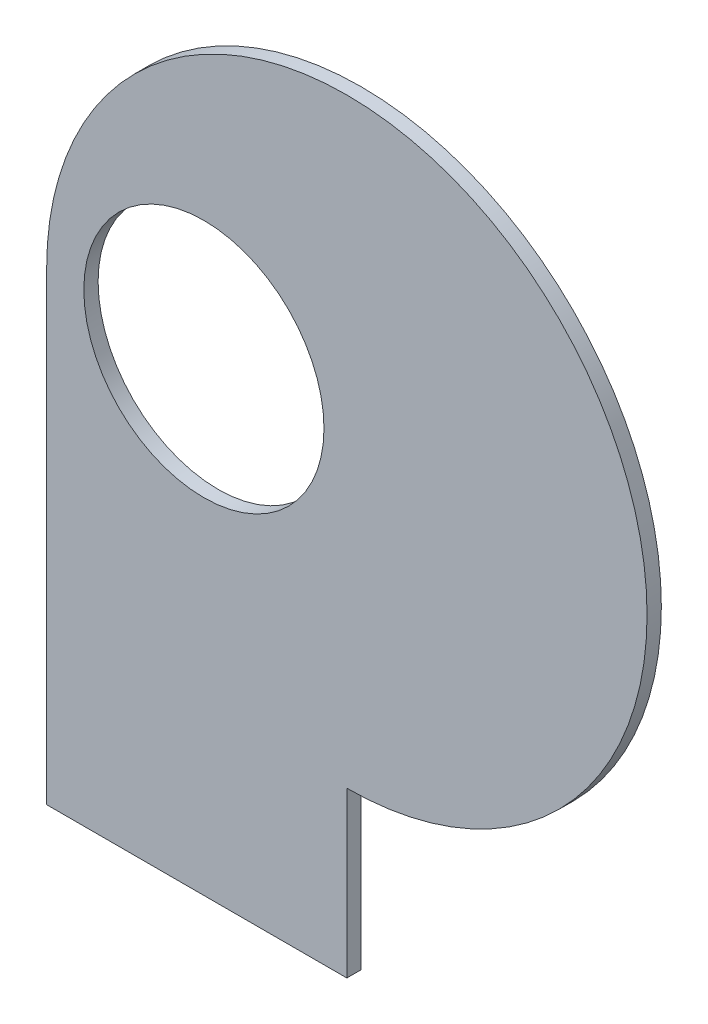
SolidWorks part; units mm, degrees
ref_plane "Front Plane" through (0, 0, 0) normal (0, 0, 1) x (1, 0, 0)
ref_plane "Top Plane" through (0, 0, 0) normal (0, 1, 0) x (1, 0, 0)
ref_plane "Right Plane" through (0, 0, 0) normal (1, 0, 0) x (0, 0, -1)
sketch "Sketch1" plane through (0, 0, 0) normal (0, 0, 1) x (1, 0, 0)
  line L0 (0, 0) -> (31.75, 0) construction
  line L1 (-34.925, 0) -> (-34.925, -63.5)
  line L4 (98.425, -64.8339) -> (98.425, 0)
  line L7 (-34.925, -63.5) -> (-34.925, -103.175)
  line L8 (-34.925, -103.175) -> (98.425, -103.175)
  line L9 (98.425, -64.8339) -> (98.425, -103.175)
  line L10 (-34.925, -63.5) -> (98.425, -103.175) construction
  line L11 (-34.925, -103.175) -> (98.425, -64.8339) construction
  circle A0 centre (0, 0) radius 25.4 construction
  circle A1 centre (0, 0) radius 26.67
  circle A2 centre (31.75, 0) radius 63.5 construction
  arc A3 (98.425, 0) -> (-34.925, 0) centre (31.75, 0) ccw
  circle A4 centre (31.75, 0) radius 66.675 construction
  point P16 (32.89, -83.6767)
  dimension "D1" = 50.8
  dimension "D3" = 127
  dimension "D6" = 103.175
  dimension "D4" = 31.75
  dimension "D2" = 1.27
  dimension "D5" = 3.175
extrude "Boss-Extrude1" add sketch "Sketch1" along normal blind 3.175
sketch "Sketch2" plane through (0, 0, 3.175) normal (0, 0, 1) x (1, 0, 0)
  line L0 (31.75, -66.675) -> (31.75, -103.175)
  line L1 (-34.925, -103.175) -> (98.425, -103.175) construction
  line L2 (31.75, -103.175) -> (98.425, -103.175)
  line L3 (98.425, -103.175) -> (98.425, 0)
  arc A0 (31.75, -66.675) -> (98.425, 0) centre (31.75, 0) ccw
extrude "Cut-Extrude1" cut sketch "Sketch2" against normal up to next
